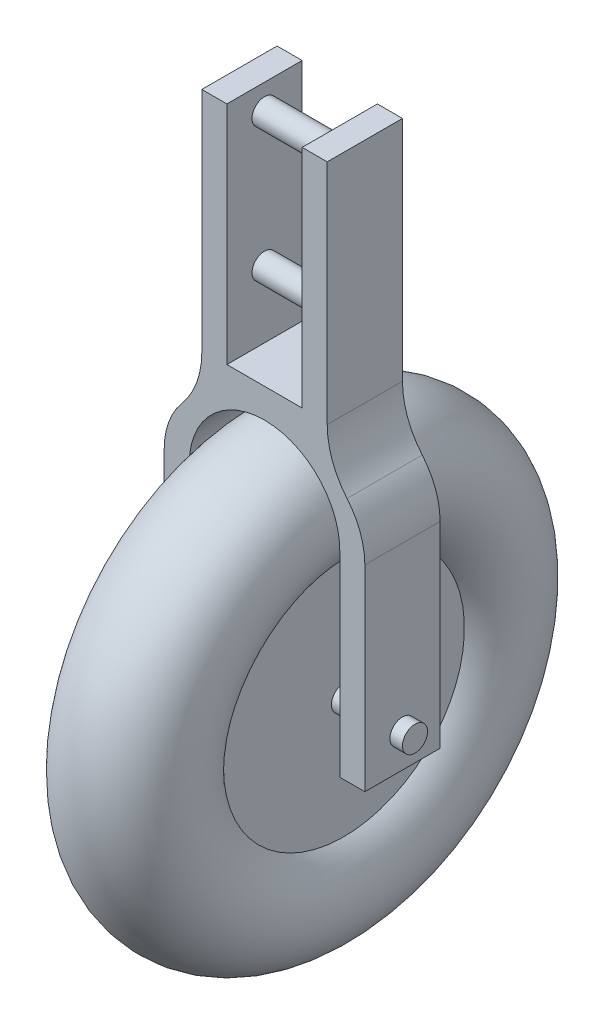
SolidWorks part; units mm, degrees
material "1060 Alloy"
ref_plane "Front" through (0, 0, 0) normal (0, 0, 1) x (1, 0, 0)
ref_plane "Top" through (0, 0, 0) normal (0, 1, 0) x (1, 0, 0)
ref_plane "Right" through (0, 0, 0) normal (1, 0, 0) x (0, 0, -1)
sketch "Sketch1" plane through (0, 0, 0) normal (0, 0, 1) x (1, 0, 0)
  line L0 (0, 0) -> (0, 27) construction
  line L1 (-7.5, 27) -> (-4.5, 27)
  line L2 (-4.5, 27) -> (-4.5, 0)
  line L3 (-4.5, 0) -> (4.5, 0)
  line L4 (-7.5, 27) -> (-7.5, -0.222)
  line L5 (-12, -36) -> (-12, -12.5)
  line L6 (-12, -36) -> (-9, -36)
  line L7 (-9, -36) -> (-9, -12.5)
  line L8 (12, -36) -> (9, -36)
  line L9 (12, -36) -> (12, -12.5)
  line L10 (9, -36) -> (9, -12.5)
  line L11 (4.5, 27) -> (4.5, 0)
  line L12 (7.5, 27) -> (7.5, -0.222)
  line L13 (7.5, 27) -> (4.5, 27)
  arc A0 (-9, -12.5) -> (0, -3.5) centre (0, -12.5) cw
  arc A1 (-12, -12.5) -> (-9.8684, -6.6841) centre (-3, -12.5) cw
  arc A2 (-7.5, -0.222) -> (-9.8684, -6.6841) centre (-17.5, -0.222) cw
  arc A3 (9, -12.5) -> (0, -3.5) centre (0, -12.5) ccw
  arc A4 (12, -12.5) -> (9.8684, -6.6841) centre (3, -12.5) ccw
  arc A5 (7.5, -0.222) -> (9.8684, -6.6841) centre (17.5, -0.222) ccw
  point P7 (-12.1417, 4.545)
  point P16 (-9.1417, 12.7188)
  point P18 (-7.5, 14.4001)
  point P19 (-7.5, 13.625)
  point P20 (-7.5, 14.8905)
  point P22 (-12.0478, 4.5449)
  point P23 (-9, -18.2414)
  point P24 (0, 0)
  point P25 (0, 0)
  point P26 (0, 0)
  point P27 (0, 0)
  point P28 (0, -3.5)
  point P29 (-7.5, -1.0626)
  dimension "D7" = 10
  dimension "D1" = 3
  dimension "D2" = 27
  dimension "D3" = 9
  dimension "D4" = 3.5
  dimension "D5" = 36
  dimension "D6" = 3
  dimension "D8" = 18
extrude "Boss-Extrude1" add sketch "Sketch1" along normal blind 9
sketch "Sketch2" plane through (7.5, 0, 0) normal (1, 0, 0) x (0, 0, -1)
  line L0 (-9, 27) -> (0, 27) construction
  circle A0 centre (-4.5, 24) radius 1.5
  circle A1 centre (-4.5, 8) radius 1.5
  point P4 (0, 0)
  point P5 (0, 0)
  point P8 (-4.5, 27)
  dimension "D1" = 3
  dimension "D2" = 3
  dimension "D3" = 16
ref_plane "Plane1" through (0, 0, 4.5) normal (0, 0, 1) x (1, 0, 0)
sketch "Sketch3" plane through (0, 0, 0) normal (1, 0, 0) x (0, 0, -1)
  line L0 (-9, -36) -> (0, -36) construction
  circle A0 centre (-4.5, -32) radius 1.5
  point P2 (0, 0)
  point P5 (-4.5, -36)
  dimension "D1" = 3
  dimension "D2" = 4
extrude "Boss-Extrude2" add sketch "Sketch3" along normal mid plane 27
sketch "Sketch4" plane through (0, 0, 4.5) normal (0, 0, 1) x (1, 0, 0)
  line L0 (0, -33.5) -> (0, -25.0754) construction
  line L1 (-9, -33.5) -> (9, -33.5) construction
  line L2 (-5.4483, -4.5) -> (5.9552, -4.5) construction
  line L3 (-13.5, -32) -> (13.5, -32) construction
  line L4 (-13.5, -30.5) -> (-13.5, -33.5) construction
  line L5 (13.5, -33.5) -> (13.5, -30.5) construction
  line L7 (-5, -32) -> (5, -32)
  line L8 (-5, -32) -> (-5, -17.5902)
  line L10 (5, -32) -> (5, -17.5902)
  arc A0 (5, -17.5902) -> (-5, -17.5902) centre (0, -12) ccw
  point P19 (0, -32)
  dimension "D1" = 27.5
  dimension "D2" = 15
  dimension "D3" = 10
revolve "Revolve1" add sketch "Sketch4" angle 360 about L3
extrude "Boss-Extrude3" add sketch "Sketch2" against normal up to surface (15 mm away) up to face at (-7.5, 13.389, 4.5)
